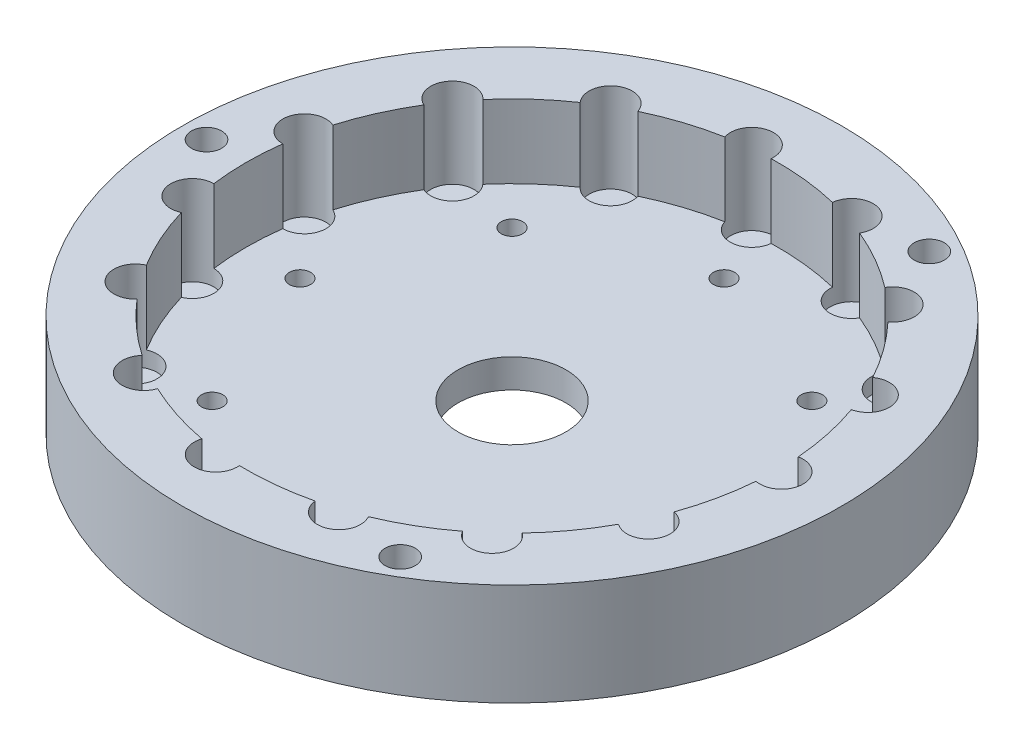
SolidWorks part; units mm, degrees
ref_plane "Front Plane" through (0, 0, 0) normal (0, 0, 1) x (1, 0, 0)
ref_plane "Top Plane" through (0, 0, 0) normal (0, 1, 0) x (1, 0, 0)
ref_plane "Right Plane" through (0, 0, 0) normal (1, 0, 0) x (0, 0, -1)
sketch "Sketch1" plane through (0, 0, 0) normal (0, 1, 0) x (1, 0, 0)
  line L0 (0, 0) -> (-42.5, 0) construction
  circle A0 centre (0, 0) radius 7.5
  circle A1 centre (0, 0) radius 45.85
  circle A2 centre (0, 0) radius 37.5 construction
  circle A3 centre (37.5, 0) radius 3
  circle A4 centre (34.258, 15.2526) radius 3
  circle A5 centre (25.0924, 27.8679) radius 3
  circle A6 centre (11.5881, 35.6646) radius 3
  circle A7 centre (-3.9198, 37.2946) radius 3
  circle A8 centre (-18.75, 32.476) radius 3
  circle A9 centre (-30.3381, 22.0419) radius 3
  circle A10 centre (-36.6805, 7.7967) radius 3
  circle A11 centre (-36.6805, -7.7967) radius 3
  circle A12 centre (-30.3381, -22.0419) radius 3
  circle A13 centre (-18.75, -32.476) radius 3
  circle A14 centre (-3.9198, -37.2946) radius 3
  circle A15 centre (11.5881, -35.6646) radius 3
  circle A16 centre (25.0924, -27.8679) radius 3
  circle A17 centre (34.258, -15.2526) radius 3
  circle A19 centre (0, 0) radius 29.5 construction
  circle A20 centre (29.5, 0) radius 1.48
  circle A21 centre (20.8597, -20.8597) radius 1.48
  circle A22 centre (0, -29.5) radius 1.48
  circle A23 centre (-20.8597, -20.8597) radius 1.48
  circle A24 centre (-29.5, 0) radius 1.48
  circle A25 centre (-20.8597, 20.8597) radius 1.48
  circle A26 centre (0, 29.5) radius 1.48
  circle A27 centre (20.8597, 20.8597) radius 1.48
  arc A28 (36.8833, 2.9359) -> (34.8888, 12.3197) centre (0, 0) ccw
  arc A29 (34.8888, -12.3197) -> (36.8833, -2.9359) centre (0, 0) ccw
  arc A30 (26.8616, -25.4451) -> (32.5004, -17.6839) centre (0, 0) ccw
  arc A31 (14.1898, -34.1709) -> (22.4979, -29.3742) centre (0, 0) ccw
  arc A32 (-0.9355, -36.9882) -> (8.6053, -35.9854) centre (0, 0) ccw
  arc A33 (-15.8991, -33.4099) -> (-6.7752, -36.3744) centre (0, 0) ccw
  arc A34 (-28.1135, -24.0547) -> (-20.9843, -30.4739) centre (0, 0) ccw
  arc A35 (-35.4669, -10.5403) -> (-31.5649, -19.3043) centre (0, 0) ccw
  arc A36 (-36.6878, 4.7967) -> (-36.6878, -4.7967) centre (0, 0) ccw
  arc A37 (-31.5649, 19.3043) -> (-35.4669, 10.5403) centre (0, 0) ccw
  arc A38 (-20.9843, 30.4739) -> (-28.1135, 24.0547) centre (0, 0) ccw
  arc A39 (-6.7752, 36.3744) -> (-15.8991, 33.4099) centre (0, 0) ccw
  arc A40 (8.6053, 35.9854) -> (-0.9355, 36.9882) centre (0, 0) ccw
  arc A41 (22.4979, 29.3742) -> (14.1898, 34.1709) centre (0, 0) ccw
  arc A42 (32.5004, 17.6839) -> (26.8616, 25.4451) centre (0, 0) ccw
  circle A43 centre (-42.5, 0) radius 2.1
  circle A44 centre (21.25, 36.8061) radius 2.1
  circle A45 centre (21.25, -36.8061) radius 2.1
  point P38 (0, 0)
  point P57 (0, 0)
  point P87 (0, 0)
  point P92 (0, 0)
  dimension "D2" = 15
  dimension "D3" = 75
  dimension "D4" = 91.7
  dimension "D5" = 6
  dimension "D8" = 2.96
  dimension "D9" = 59
  dimension "D6" = 37
  dimension "D12" = 4.2
  dimension "D11" = 42.5
  dimension "D1" = 15
  dimension "D7" = 8
  dimension "D10" = 15
  dimension "D13" = 3
extrude "Boss-Extrude1" add sketch "Sketch1" against normal blind 4 contours A4 A42 A5 A41 A6 A40 A7 A39 A8 A38 A9 A37 A10 A36 A11 A35 A12 A34 A13 A33 A14 A32 A15 A31 A16 A30 A17 A29 A3 A28 A0 A20 A21 A22 A23 A24 A25 A26 A27 | A3 | A17 | A4 | A5 | A6 | A7 | A8 | A9 | A10 | A11 | A12 | A13 | A14 | A15 | A16 | A1 A42 A4 A28 A3 A29 A17 A30 A16 A31 A15 A32 A14 A33 A13 A34 A12 A35 A11 A36 A10 A37 A9 A38 A8 A39 A7 A40 A6 A41 A5 | A22 | A23 | A24 | A25 | A26 | A27 | A20 | A21 region at (-45.7203, 0, 0) region at (37.5, 0, 0) region at (33.4543, 0, 0) region at (34.258, 0, -15.2526) region at (34.258, 0, 15.2526) region at (25.0924, 0, -27.8679) region at (25.0924, 0, 27.8679) region at (11.5881, 0, -35.6646) region at (11.5881, 0, 35.6646) region at (-3.9198, 0, -37.2946) region at (-3.9198, 0, 37.2946) region at (-18.75, 0, -32.476) region at (-18.75, 0, 32.476) region at (-30.3381, 0, -22.0419) region at (-30.3381, 0, 22.0419) region at (-36.6805, 0, -7.7967) region at (-36.6805, 0, 7.7967) region at (29.5, 0, 0) region at (20.8597, 0, 20.8597) region at (0, 0, 29.5) region at (-20.8597, 0, 20.8597) region at (-29.5, 0, 0) region at (-20.8597, 0, -20.8597) region at (0, 0, -29.5) region at (20.8597, 0, -20.8597)
extrude "Cut-Extrude1" cut sketch "Sketch1<6>" against normal blind 2.22 contours A24 | A25 | A26 | A27 | A20 | A21 | A22 | A23 | A10 | A11 | A9 | A12 | A13 | A14 | A15 | A16 | A17 | A3 | A4 | A5 | A6 | A7 | A8 region at (37.5, 0, 0) region at (34.258, 0, -15.2526) region at (34.258, 0, 15.2526) region at (25.0924, 0, -27.8679) region at (25.0924, 0, 27.8679) region at (11.5881, 0, -35.6646) region at (11.5881, 0, 35.6646) region at (-3.9198, 0, -37.2946) region at (-3.9198, 0, 37.2946) region at (-18.75, 0, -32.476) region at (-18.75, 0, 32.476) region at (-30.3381, 0, -22.0419) region at (-30.3381, 0, 22.0419) region at (-36.6805, 0, -7.7967) region at (-36.6805, 0, 7.7967) region at (29.5, 0, 0) region at (20.8597, 0, 20.8597) region at (0, 0, 29.5) region at (-20.8597, 0, 20.8597) region at (-29.5, 0, 0) region at (-20.8597, 0, -20.8597) region at (0, 0, -29.5) region at (20.8597, 0, -20.8597)
sketch "Sketch1<6>" plane through (0, 0, 0) normal (0, 1, 0) x (1, 0, 0) same geometry as "Sketch1"
extrude "Boss-Extrude2" add sketch "Sketch1<7>" along normal blind 10.22 contours A1 A42 A4 A28 A3 A29 A17 A30 A16 A31 A15 A32 A14 A33 A13 A34 A12 A35 A11 A36 A10 A37 A9 A38 A8 A39 A7 A40 A6 A41 A5 region at (-45.7203, 0, 0)
sketch "Sketch1<7>" plane through (0, 0, 0) normal (0, 1, 0) x (1, 0, 0) same geometry as "Sketch1"
equation "\"bearing_21_OD\"= 21mm"
equation "\"D2@Sketch1\"=\"bearing_15_OD\"+\"bearing_21_outer_clearance\""
equation "\"pin_cirlce_diameter\"= 75mm"
equation "\"D3@Sketch1\"=\"pin_cirlce_diameter\""
equation "\"pin_diam\"= 6mm"
equation "\"D5@Sketch1\"=\"pin_diam\""
equation "\"gear_thickness\"= 4mm"
equation "\"ball_bearing_diam\"= 2.96mm"
equation "\"bearing_21_outer_clearance\"= 0mm'change this"
equation "\"bearing_15_OD\"= 15mm"
equation "\"bearing_15_outer_clearance\"= 0mm'change this"
equation "\"D8@Sketch1\"=\"ball_bearing_diam\""
equation "\"D1@Cut-Extrude1\"=\"ball_bearing_diam\"*0.75"
equation "\"thrust_bearing_thickness\"= 5mm'measure this irl and change"
equation "\"D1@Boss-Extrude2\"=\"ball_bearing_diam\"*0.75mm+2*\"gear_thickness\""
